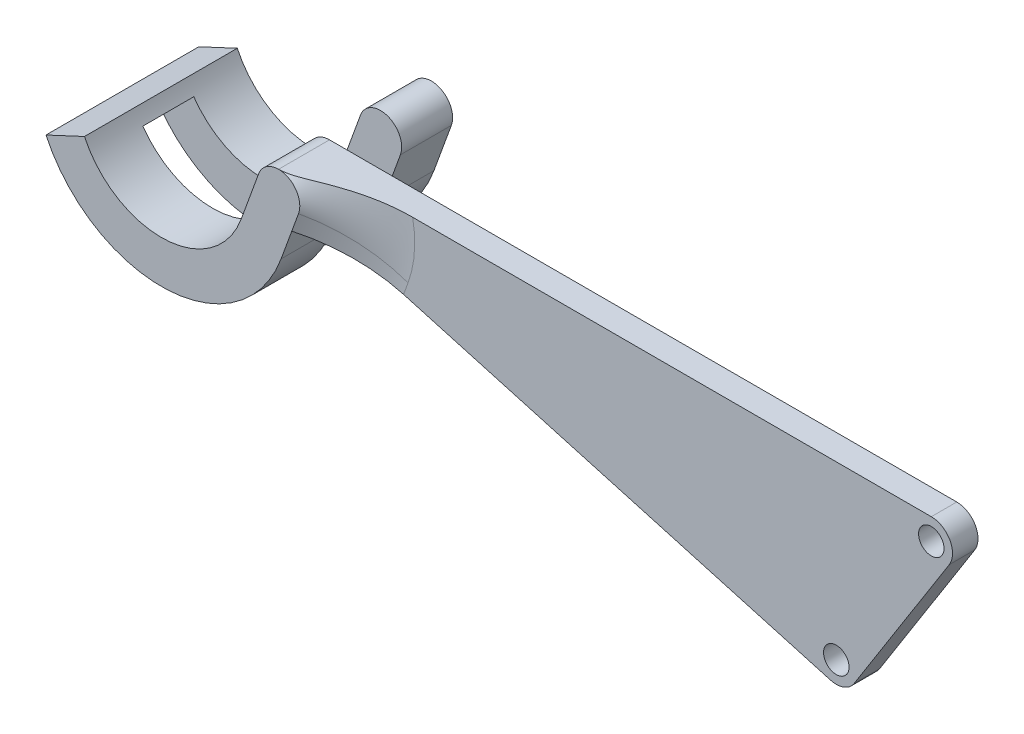
SolidWorks part; units mm, degrees
ref_plane "前基準面" through (0, 0, 0) normal (0, 0, 1) x (1, 0, 0)
ref_plane "上基準面" through (0, 0, 0) normal (0, 1, 0) x (1, 0, 0)
ref_plane "右基準面" through (0, 0, 0) normal (1, 0, 0) x (0, 0, -1)
sketch "草圖1" plane through (0, 0, 0) normal (0, 0, 1) x (1, 0, 0)
  line L0 (0, 0) -> (36.94, 0) construction
  line L1 (36.94, 0) -> (31.3447, -8.8495) construction
  line L2 (31.3447, -8.8495) -> (0, 0) construction
  line L3 (0, 1.25) -> (36.94, 1.25)
  line L4 (-0.3396, -1.203) -> (31.0051, -10.0525)
  line L5 (36.94, 0) -> (37.9965, -0.668) construction
  line L6 (37.9965, -0.668) -> (32.4012, -9.5175)
  arc A0 (0, 1.25) -> (-0.3396, -1.203) centre (0, 0) ccw
  arc A1 (37.9965, -0.668) -> (36.94, 1.25) centre (36.94, 0) ccw
  arc A2 (31.0051, -10.0525) -> (32.4012, -9.5175) centre (31.3447, -8.8495) ccw
  circle A3 centre (0, 0) radius 0.75
  circle A4 centre (36.94, 0) radius 0.75
  circle A5 centre (31.3447, -8.8495) radius 0.75
  dimension "D1" = 2.5
  dimension "D5" = 1.5
  dimension "D6" = 2.5
  dimension "D2" = 32.57
  dimension "D3" = 36.94
  dimension "D4" = 10.47
extrude "填料-伸長1" add sketch "草圖1" along normal mid plane 1.5 contours L3 A1 L6 A2 L4 A0
sketch "草圖2" plane through (0, 0, 0.75) normal (0, 0, 1) x (1, 0, 0)
  circle A0 centre (31.3447, -8.8495) radius 0.75 construction
  circle A1 centre (36.94, 0) radius 0.75 construction
  circle A2 centre (0, 0) radius 0.75 construction
  circle A3 centre (31.3447, -8.8495) radius 0.75
  circle A4 centre (36.94, 0) radius 0.75
  circle A5 centre (0, 0) radius 0.75
extrude "除料-伸長1" cut sketch "草圖2" against normal blind 11.5
sketch "草圖3" plane through (0, 0, -0.75) normal (0, 0, -1) x (-1, 0, 0)
  line L0 (1.1746, 0.4275) -> (2.2007, -2.3916)
  line L1 (2.2007, -2.3916) -> (-0.1486, -3.2466)
  line L2 (-0.1486, -3.2466) -> (-1.1746, -0.4275)
  line L3 (11.4307, -2.7945) -> (13.6964, -3.8511)
  line L4 (0, 1.25) -> (-36.94, 1.25) construction
  line L5 (11.4307, -2.7945) -> (15.8357, 6.6521) construction
  arc A2 (1.1746, 0.4275) -> (-1.1746, -0.4275) centre (0, 0) ccw
  arc A3 (2.2007, -2.3916) -> (11.4307, -2.7945) centre (6.8991, -0.6815) ccw
  arc A4 (-0.1486, -3.2466) -> (13.6964, -3.8511) centre (6.8991, -0.6815) ccw
  arc A5 (0.3396, -1.203) -> (0, 1.25) centre (0, 0) ccw construction
  circle M7 centre (0, 0) radius 0.75
  arc M9 (0.3396, -1.203) -> (0, 1.25) centre (0, 0) ccw
  line M14 (-31.0051, -10.0525) -> (0.3396, -1.203)
  dimension "D4" = 5
  dimension "D1" = 70
  dimension "D2" = 135
  dimension "D3" = 3
extrude "填料-伸長2" add sketch "草圖3" against normal blind 3 and the other way blind 6 contours M7 | A2 L2 M9 M14 M7 | L2 L1 L0 M9 M14 | L1 A4 L3 A3 region at (-1.0794, -0.5528, -0.75) region at (-0.7507, -1.8908, -0.75) region at (-6.6745, -5.8266, -0.75) region at (0, 0, -0.75)
sketch "草圖4" plane through (0, 0, -0.75) normal (0, 0, -1) x (-1, 0, 0)
  line L1 (-0.1486, -3.2466) -> (-1.1746, -0.4275) construction
  line L2 (1.1746, 0.4275) -> (2.2007, -2.3916) construction
  line L3 (11.4307, -2.7945) -> (13.6964, -3.8511) construction
  line L4 (-0.1486, -3.2466) -> (-1.1746, -0.4275)
  line L5 (1.1746, 0.4275) -> (2.2007, -2.3916)
  line L6 (10.9949, -3.5493) -> (13.0428, -4.9833)
  line L7 (10.9949, -3.5493) -> (18.6679, 7.4088) construction
  arc A0 (2.2007, -2.3916) -> (11.4307, -2.7945) centre (6.8991, -0.6815) ccw construction
  arc A1 (-0.1486, -3.2466) -> (13.6964, -3.8511) centre (6.8991, -0.6815) ccw construction
  arc A2 (1.1746, 0.4275) -> (-1.1746, -0.4275) centre (0, 0) ccw construction
  arc A3 (2.2007, -2.3916) -> (10.9949, -3.5493) centre (6.8991, -0.6815) ccw
  arc A4 (-0.1486, -3.2466) -> (13.0428, -4.9833) centre (6.8991, -0.6815) ccw
  arc A5 (1.1746, 0.4275) -> (-1.1746, -0.4275) centre (0, 0) ccw
  dimension "D1" = 10
extrude "除料-伸長2" cut sketch "草圖4" along normal blind 3
fillet "圓角1" radius 10 2 edges at (0.9761, -0.973, 0.75) (1.0239, 0.717, 0.75)
